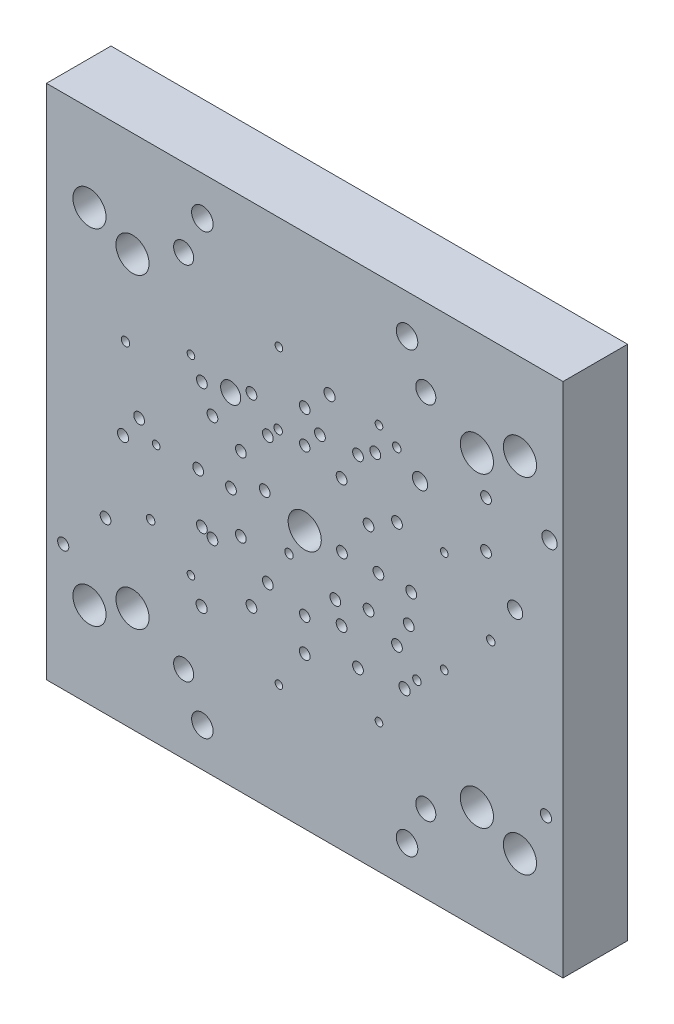
SolidWorks part; units mm, degrees
ref_plane "Front Plane" through (0, 0, 0) normal (0, 0, 1) x (1, 0, 0)
ref_plane "Top Plane" through (0, 0, 0) normal (0, 1, 0) x (1, 0, 0)
ref_plane "Right Plane" through (0, 0, 0) normal (1, 0, 0) x (0, 0, -1)
sketch "Sketch1" plane through (0, 0, 0) normal (0, 0, 1) x (1, 0, 0)
  line L1 (-152.4, 152.4) -> (152.4, 152.4)
  line L2 (-152.4, 152.4) -> (-152.4, -152.4)
  line L3 (-152.4, -152.4) -> (152.4, -152.4)
  line L4 (152.4, 152.4) -> (152.4, -152.4)
  line L5 (-152.4, 152.4) -> (152.4, -152.4) construction
  line L6 (-152.4, -152.4) -> (152.4, 152.4) construction
  point P0 (0, 0)
  dimension "D1" = 304.8
  dimension "D2" = 304.8
extrude "Boss-Extrude1" add sketch "Sketch1" along normal blind 38.1
sketch "Sketch2" plane through (0, 0, 38.1) normal (0, 0, 1) x (1, 0, 0)
  line L0 (-152.4, 0) -> (152.4, 0) construction
  line L5 (-152.4, 152.4) -> (-152.4, -152.4) construction
  line L6 (152.4, -152.4) -> (152.4, 152.4) construction
  line L7 (-152.4, -101.6) -> (152.4, -101.6) construction
  line L8 (-152.4, 101.6) -> (152.4, 101.6) construction
  line L9 (0, 101.6) -> (0, -101.6) construction
  line L10 (127, 101.6) -> (127, -101.6) construction
  line L11 (-127, 101.6) -> (-127, -101.6) construction
  circle A0 centre (-127, 101.6) radius 6.5151
  circle A1 centre (127, 101.6) radius 6.5151
  circle A2 centre (127, -101.6) radius 6.5151
  circle A3 centre (-127, -101.6) radius 6.5151
  circle A4 centre (0, 0) radius 6.5151
  dimension "D5" = 13.0302
  dimension "D1" = 101.6
  dimension "D2" = 101.6
  dimension "D3" = 127
  dimension "D4" = 127
extrude "HAAS T-Slot Holes" cut sketch "Sketch2" against normal through all
sketch "Sketch3" plane through (0, 0, 38.1) normal (0, 0, 1) x (1, 0, 0)
  circle A0 centre (-127, 101.6) radius 9.779
  circle A1 centre (127, 101.6) radius 9.779
  circle A2 centre (0, 0) radius 9.779
  circle A3 centre (127, -101.6) radius 9.779
  circle A4 centre (-127, -101.6) radius 9.779
  dimension "D1" = 19.558
extrude "HAAS Counter Bores" cut sketch "Sketch3" against normal offset from surface (22.225 mm away) 15.875 contours A0 | A1 | A2 | A3 | A4 up to face at (6.5151, 0, 0)
sketch "Sketch4" plane through (0, 0, 38.1) normal (0, 0, 1) x (1, 0, 0)
  line L0 (-127, 90.4875) -> (127, 90.4875) construction
  line L1 (-127, 30.1625) -> (127, 30.1625) construction
  line L2 (-127, 30.1625) -> (-127, -30.1625) construction
  line L3 (-127, -30.1625) -> (127, -30.1625) construction
  line L4 (127, 30.1625) -> (127, -30.1625) construction
  line L5 (-127, 30.1625) -> (127, -30.1625) construction
  line L6 (-127, -30.1625) -> (127, 30.1625) construction
  line L7 (-127, -90.4875) -> (127, -90.4875) construction
  line L8 (-101.6, 90.4875) -> (-101.6, 84.1375) construction
  line L9 (-101.6, -90.4875) -> (-101.6, -84.1375) construction
  line L10 (101.6, -90.4875) -> (101.6, -84.1375) construction
  line L11 (101.6, 90.4875) -> (101.6, 84.1375) construction
  circle A0 centre (-101.6, 90.4875) radius 6.5151
  circle A1 centre (101.6, 90.4875) radius 6.5151
  circle A2 centre (-101.6, -90.4875) radius 6.5151
  circle A3 centre (101.6, -90.4875) radius 6.5151
  point P0 (0, 0)
  dimension "D9" = 13.0302
  dimension "D1" = 60.325
  dimension "D2" = 254
  dimension "D5" = 203.2
  dimension "D6" = 25.4
  dimension "D7" = 203.2
  dimension "D8" = 6.35
  dimension "D3" = 60.325
  dimension "D4" = 60.325
extrude "Tormach T-Slot Holes" cut sketch "Sketch4" against normal through all
sketch "Sketch5" plane through (0, 0, 38.1) normal (0, 0, 1) x (1, 0, 0)
  circle A0 centre (-101.6, 90.4875) radius 9.779
  circle A1 centre (101.6, 90.4875) radius 9.779
  circle A2 centre (101.6, -90.4875) radius 9.779
  circle A3 centre (-101.6, -90.4875) radius 9.779
  dimension "D1" = 19.558
extrude "Tormach Counter bores" cut sketch "Sketch5" against normal up to surface (22.225 mm away) up to face at (-117.221, 101.6, 15.875)
sketch "Sketch6" plane through (0, 0, 38.1) normal (0, 0, 1) x (1, 0, 0)
  circle A0 centre (0, 0) radius 43.5 construction
  circle A1 centre (0, 43.5) radius 3.0734
  circle A2 centre (0, -43.5) radius 3.0734
  dimension "D1" = 87.0001
  dimension "D2" = 6.1468
extrude "Sprocket Locating Holes" cut sketch "Sketch6" against normal blind 6.35
sketch "Sketch7" plane through (0, 0, 38.1) normal (0, 0, 1) x (1, 0, 0)
  circle A0 centre (0, 0) radius 43.5 construction
  circle A2 centre (43.5, 0) radius 3.175
  circle A4 centre (37.6721, -21.75) radius 3.175
  circle A5 centre (21.75, -37.6721) radius 3.175
  circle A6 centre (0, -43.5) radius 3.175 [skipped]
  circle A7 centre (-21.75, -37.6721) radius 3.175
  circle A8 centre (-37.6721, -21.75) radius 3.175
  circle A9 centre (-43.5, 0) radius 3.175
  circle A10 centre (-37.6721, 21.75) radius 3.175
  circle A11 centre (-21.75, 37.6721) radius 3.175
  circle A12 centre (0, 43.5) radius 3.175 [skipped]
  circle A13 centre (21.75, 37.6721) radius 3.175
  circle A14 centre (37.6721, 21.75) radius 3.175
  point P31 (0, 0)
  dimension "D1" = 87.0001
  dimension "D2" = 6.35
  dimension "D3" = 12
extrude "Sprocket Mounting clearance holes" cut sketch "Sketch7" against normal blind 9.525
sketch "Sketch8" plane through (0, 0, 38.1) normal (0, 0, 1) x (1, 0, 0)
  line L1 (-71.4375, 106.4641) -> (71.4375, 106.4641) construction
  line L2 (-71.4375, 106.4641) -> (-71.4375, -106.4641) construction
  line L3 (-71.4375, -106.4641) -> (71.4375, -106.4641) construction
  line L4 (71.4375, 106.4641) -> (71.4375, -106.4641) construction
  line L5 (-71.4375, 106.4641) -> (71.4375, -106.4641) construction
  line L6 (-71.4375, -106.4641) -> (71.4375, 106.4641) construction
  circle A0 centre (-71.4375, 106.4641) radius 5.9182
  circle A1 centre (71.4375, 106.4641) radius 5.9182
  circle A2 centre (71.4375, -106.4641) radius 5.9182
  circle A3 centre (-71.4375, -106.4641) radius 5.9182
  point P0 (0, 0)
  dimension "D3" = 11.8364
  dimension "D1" = 142.875
  dimension "D2" = 212.9282
extrude "1/2-13 Tapped Holes" cut sketch "Sketch8" against normal blind 19.05
sketch "Sketch9" plane through (0, 0, 38.1) normal (0, 0, 1) x (1, 0, 0)
  circle A0 centre (-117.5189, -52.2876) radius 3.175
  circle A1 centre (-60.6634, -28.4101) radius 3.175
  circle A2 centre (-60.6634, 45.677) radius 3.175
  circle A3 centre (-23.6198, 8.6335) radius 3.175
  circle A4 centre (-97.707, 8.6335) radius 3.175
  circle A5 centre (18.0623, -26.1797) radius 3.175
  circle A6 centre (21.9762, 0) radius 3.175
  circle A7 centre (61.3833, -17.3739) radius 3.175
  circle A8 centre (106.976, 70.3959) radius 3.175
  circle A9 centre (106.976, 42.9004) radius 3.175
  circle A10 centre (144.4539, 67.4373) radius 4.5
  circle A11 centre (124.1092, 21.6131) radius 4.5
  circle A12 centre (68.0681, 59.3279) radius 4.5
  circle A13 centre (58.9353, -51.2652) radius 3.3
  circle A14 centre (-142.4923, -78.095) radius 3.3
  circle A15 centre (-105.7351, 43.7713) radius 2.5
  circle A16 centre (-90.8975, -39.8642) radius 2.5
  circle A17 centre (-9.2711, -16.3656) radius 2.5
  circle A18 centre (-15.6655, 43.8657) radius 2.5
  circle A20 centre (14.6267, 76.8405) radius 3.3
  circle A21 centre (8.9855, 53.4682) radius 3.175
  circle A22 centre (41.6559, 60.6579) radius 3.175
extrude "SSB Holes" cut sketch "Sketch9" against normal blind 19.05
ref_axis "Axis1" through (0, 0, 0) along (0, 0, 1)
sketch "Sketch10" plane through (0, 0, 38.1) normal (0, 0, 1) x (1, 0, 0)
  circle A0 centre (0, 0) radius 62.865 construction
  circle A1 centre (0, 62.865) radius 3.175
  circle A13 centre (31.4325, 54.4427) radius 3.175
  circle A14 centre (54.4427, 31.4325) radius 3.175
  circle A15 centre (62.865, 0) radius 3.175
  circle A16 centre (54.4427, -31.4325) radius 3.175
  circle A17 centre (31.4325, -54.4427) radius 3.175
  circle A18 centre (0, -62.865) radius 3.175
  circle A19 centre (-31.4325, -54.4427) radius 3.175
  circle A20 centre (-54.4427, -31.4325) radius 3.175
  circle A21 centre (-62.865, 0) radius 3.175
  circle A22 centre (-54.4427, 31.4325) radius 3.175
  circle A23 centre (-31.4325, 54.4427) radius 3.175
  point P30 (0, 0)
  point P56 (0, 0)
  dimension "D1" = 125.73
  dimension "D2" = 6.35
  dimension "D4" = 12
extrude "Sprocket Countersunk Holes" cut sketch "Sketch10" against normal blind 19.05
sketch "Sketch12" plane through (0, 0, 38.1) normal (0, 0, 1) x (1, 0, 0)
  circle A0 centre (-107.2144, -4.9977) radius 3.3
  circle A1 centre (-60.8212, -69.1392) radius 3.3
  circle A2 centre (142.3129, -74.567) radius 3.3
  circle A4 centre (54.3307, 69.7186) radius 2.4964
  circle A5 centre (109.7823, -1.2607) radius 2.5
  circle A6 centre (66.2094, -43.3332) radius 2.5
  circle A7 centre (-43.6886, 48.7489) radius 5.9182
  circle A8 centre (-71.4375, 106.4641) radius 5.9182 construction
extrude "DSB Holes" cut sketch "Sketch12" against normal blind 19.05
sketch "Brake Rotor Toe Clamp Holes" plane through (0, 0, 38.1) normal (0, 0, 1) x (1, 0, 0)
  line L0 (-55.0143, 117.9786) -> (55.0143, -117.9786) construction
  line L1 (55.0143, 117.9786) -> (-55.0143, -117.9786) construction
  line L2 (-55.0143, 117.9786) -> (-60.3816, 129.4887) construction
  line L3 (55.0143, 117.9786) -> (60.3816, 129.4887) construction
  line L4 (-55.0143, -117.9786) -> (-60.3816, -129.4887) construction
  line L5 (55.0143, -117.9786) -> (60.3816, -129.4887) construction
  line L6 (0, 0) -> (192.0367, 0) construction
  line L7 (0, 0) -> (-160.9096, 0) construction
  line L8 (0, 0) -> (0, 219.8313) construction
  line L9 (0, 0) -> (-215.8918, 38.0675) construction
  circle A0 centre (0, 0) radius 130.175 construction
  circle A6 centre (-60.3816, 129.4887) radius 6.35
  circle A7 centre (60.3816, 129.4887) radius 6.35
  circle A8 centre (60.3816, -129.4887) radius 6.35
  circle A9 centre (-60.3816, -129.4887) radius 6.35
  circle A10 centre (-87.63, 0) radius 2.3813 construction
  circle A12 centre (-74.93, 0) radius 2.3813 construction
  circle A13 centre (-80.0452, 14.1141) radius 2.3813
  circle A14 centre (-70.4112, 25.6276) radius 2.3812 construction
  circle A15 centre (-70.3905, 40.64) radius 2.3812 construction
  circle A16 centre (-82.3453, 29.9712) radius 2.3812 construction
  circle A17 centre (-57.3997, 48.1641) radius 2.3813 construction
  circle A18 centre (-52.2458, 62.2641) radius 2.3812
  circle A19 centre (-67.1285, 56.3275) radius 2.3812 construction
  circle A20 centre (-37.465, 64.8913) radius 2.3813 construction
  circle A21 centre (-27.7994, 76.3782) radius 2.3813 construction
  circle A22 centre (-43.815, 75.8898) radius 2.3813 construction
  circle A23 centre (-13.0115, 73.7916) radius 2.3813 construction
  circle A24 centre (0, 81.28) radius 2.3813
  circle A25 centre (-15.2168, 86.2987) radius 2.3813 construction
  circle A26 centre (13.0115, 73.7916) radius 2.3812 construction
  circle A27 centre (27.7994, 76.3782) radius 2.3812 construction
  circle A28 centre (15.2168, 86.2987) radius 2.3813 construction
  circle A29 centre (37.465, 64.8913) radius 2.3812 construction
  circle A30 centre (52.2458, 62.2641) radius 2.3813
  circle A31 centre (43.815, 75.8898) radius 2.3812 construction
  circle A32 centre (57.3997, 48.1641) radius 2.3813 construction
  circle A33 centre (70.3905, 40.64) radius 2.3813 construction
  circle A34 centre (67.1285, 56.3275) radius 2.3813 construction
  circle A35 centre (70.4112, 25.6276) radius 2.3813 construction
  circle A36 centre (80.0452, 14.1141) radius 2.3813
  circle A37 centre (82.3453, 29.9712) radius 2.3813 construction
  circle A38 centre (74.93, 0) radius 2.3813 construction
  circle A39 centre (80.0452, -14.1141) radius 2.3813 construction
  circle A40 centre (87.63, 0) radius 2.3813 construction
  circle A41 centre (70.4112, -25.6276) radius 2.3812 construction
  circle A42 centre (70.3905, -40.64) radius 2.3813
  circle A43 centre (82.3453, -29.9712) radius 2.3812 construction
  circle A44 centre (57.3997, -48.1641) radius 2.3813 construction
  circle A45 centre (52.2458, -62.2641) radius 2.3813 construction
  circle A46 centre (67.1285, -56.3275) radius 2.3812 construction
  circle A47 centre (37.465, -64.8913) radius 2.3813 construction
  circle A48 centre (27.7994, -76.3782) radius 2.3813
  circle A49 centre (43.815, -75.8898) radius 2.3813 construction
  circle A50 centre (13.0115, -73.7916) radius 2.3813 construction
  circle A51 centre (0, -81.28) radius 2.3812 construction
  circle A52 centre (15.2168, -86.2987) radius 2.3813 construction
  circle A53 centre (-13.0115, -73.7916) radius 2.3813 construction
  circle A54 centre (-27.7994, -76.3782) radius 2.3813
  circle A55 centre (-15.2168, -86.2987) radius 2.3813 construction
  circle A56 centre (-37.465, -64.8913) radius 2.3813 construction
  circle A57 centre (-52.2458, -62.2641) radius 2.3813 construction
  circle A58 centre (-43.815, -75.8898) radius 2.3812 construction
  circle A59 centre (-57.3997, -48.1641) radius 2.3813 construction
  circle A60 centre (-70.3905, -40.64) radius 2.3813
  circle A61 centre (-67.1285, -56.3275) radius 2.3813 construction
  circle A62 centre (-70.4112, -25.6276) radius 2.3813 construction
  circle A63 centre (-80.0452, -14.1141) radius 2.3813 construction
  circle A64 centre (-82.3453, -29.9712) radius 2.3813 construction
  point P27 (0, 0)
  point P130 (0, 0)
  dimension "D1" = 260.35
  dimension "D2" = 12.7
  dimension "D3" = 12.7
  dimension "D4" = 12.7
  dimension "D5" = 12.7
  dimension "D17" = 4.7625
  dimension "D18" = 81.28
  dimension "D19" = 18
  dimension "D14" = 4.7625
  dimension "D15" = 4.7625
  dimension "D6" = 12.7
  dimension "D7" = 12.7
  dimension "D8" = 12.7
  dimension "D9" = 12.7
  dimension "D10" = 65
  dimension "D11" = 65
  dimension "D12" = 87.63
  dimension "D13" = 12.7
  dimension "D16" = 10
hole_wizard "Rotor Clamp Bolts" positions "Sketch15" profile "Sketch16" hole size "M4" standard "AS"
sketch "Sketch15" plane through (0, 0, 38.1) normal (0, 0, 1) x (1, 0, 0)
  point P0 (-87.63, 0)
  point P3 (-67.1285, -56.3275)
  point P6 (-15.2168, -86.2987)
  point P9 (43.815, -75.8898)
  point P12 (82.3453, -29.9712)
  point P15 (82.3453, 29.9712)
  point P18 (43.815, 75.8898)
  point P21 (-15.2168, 86.2987)
  point P24 (-67.1285, 56.3275)
sketch "Sketch16" plane through (-87.63, 0, 38.1) normal (1, 0, 0) x (0, -1, 0)
  line L0 (0, 0) -> (0, 20.4019)
  line L1 (0, 20.4019) -> (2.25, 19.05)
  line L2 (2.25, 19.05) -> (2.25, 0)
  line L5 (2.25, 0) -> (0, 0)
  line L10 (0, 20.4019) -> (-2.25, 19.05) construction
  line L11 (0, -6.35) -> (0, 107.95) construction
  dimension "Hole Dia." = 4.5
  dimension "Hole Depth" = 19.05
  dimension "Drill Angle" = 118
extrude "Outer Toe Clamp" cut sketch "Brake Rotor Toe Clamp Holes" against normal blind 19.05 contours A8 | A9 | A7 | A6
equation "\"boltRotor\"=0.75"
equation "\"bolt\"=0.51159"
